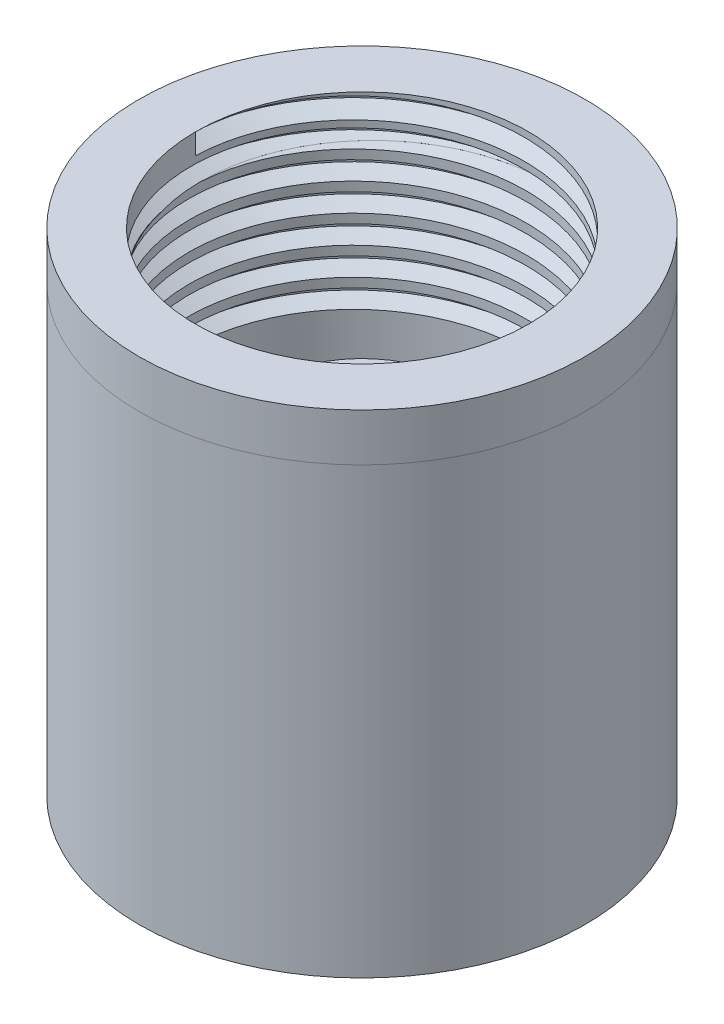
SolidWorks part; units mm, degrees
ref_plane "Спереди" through (0, 0, 0) normal (0, 0, 1) x (1, 0, 0)
ref_plane "Сверху" through (0, 0, 0) normal (0, 1, 0) x (1, 0, 0)
ref_plane "Справа" through (0, 0, 0) normal (1, 0, 0) x (0, 0, -1)
sketch "Эскиз1" plane through (0, 0, 0) normal (0, 1, 0) x (1, 0, 0)
  circle A0 centre (0, 0) radius 14.05
  dimension "D1" = 28.1
extrude "Бобышка-Вытянуть2" add sketch "Эскиз1" against normal blind 28 contours A0
sketch "Эскиз2" plane through (0, 0, 0) normal (0, 1, 0) x (1, 0, 0)
  circle A0 centre (0, 0) radius 10.625
  dimension "D1" = 21.25
extrude "Вырез-Вытянуть1" cut sketch "Эскиз2" against normal blind 13.1 contours A0
sketch "Эскиз3" plane through (0, -13.1, 0) normal (0, 1, 0) x (1, 0, 0)
  circle A1 centre (0, 0) radius 5.7
  circle A2 centre (0, 0) radius 10.625 construction
  dimension "D2" = 11.4
extrude "Бобышка-Вытянуть3" add sketch "Эскиз3" along normal blind 4.6 draft 6 contours A1 draft outward yes
ref_plane "Плоскость2" through (0, 0, 0) normal (0, 1, 0) x (1, 0, 0)
sketch "Эскиз7" plane through (0, 0, 0) normal (0, 1, 0) x (1, 0, 0)
  circle A0 centre (0, 0) radius 10.5
  circle A1 centre (0, 0) radius 14.05
extrude "Бобышка-Вытянуть4" add sketch "Эскиз7" along normal blind 3 contours A0 | A1
thread "Резьба2" pitch 1.75 method cut profile "Профиль резьбы2" start angle 0, offset 0, length 11.5, pitch 1.75, diameter 21
ref_plane "Плоскость3" through (-10.5, 3, 0) normal (0, 0, 1) x (-1, 0, 0)
sketch "Профиль резьбы2" plane through (-10.5, 3, 0) normal (0, 0, 1) x (-1, 0, 0)
  line L0 (0, 0) -> (0, 1.75) construction
  line L1 (0, 0) -> (0.9472, 0.5469)
  line L2 (0.9472, 0.5469) -> (0.9472, 0.7656)
  line L3 (0.9472, 0.7656) -> (0, 1.3125)
  line L4 (0.9472, 0.6562) -> (0, 0.6562) construction
  line L11 (0, 0) -> (0, 1.3125)
  point P2 (0, 0)
  dimension "Pitch" = 1.75
  dimension "Profile_Angle" = 60
  dimension "Profile_Land" = 0.2188
  dimension "Profile_Height" = 0.9472
sketch "Эскиз14" plane through (0, 0, 0) normal (1, 0, 0) x (0, 0, -1)
  line L0 (21.712, 0) -> (-21.3879, 0)
  line L1 (15.455, 0) -> (-15.455, 0) construction
split "Разделить2" trim tools "Эскиз14" bodies to split 108 resulting bodies 110 111
ref_plane "Плоскость5" through (0, -33, 0) normal (0, -1, 0) x (-1, 0, 0)
sketch "Эскиз18" plane through (0, -33, 0) normal (0, -1, 0) x (-1, 0, 0)
  line L0 (-13.8315, 14.1869) -> (14.3992, 14.1869) construction
ref_plane "Плоскость6" through (0, -12.3795, 10.3876) normal (0, 0.766, -0.6428) x (-1, 0, 0)
sketch "Эскиз19" plane through (0, -12.3795, 10.3876) normal (0, 0.766, -0.6428) x (-1, 0, 0)
  circle A0 centre (0, -24.0766) radius 1.5
extrude "Вырез-Вытянуть3" cut sketch "Эскиз19" against normal through all both and the other way through all contours A0
